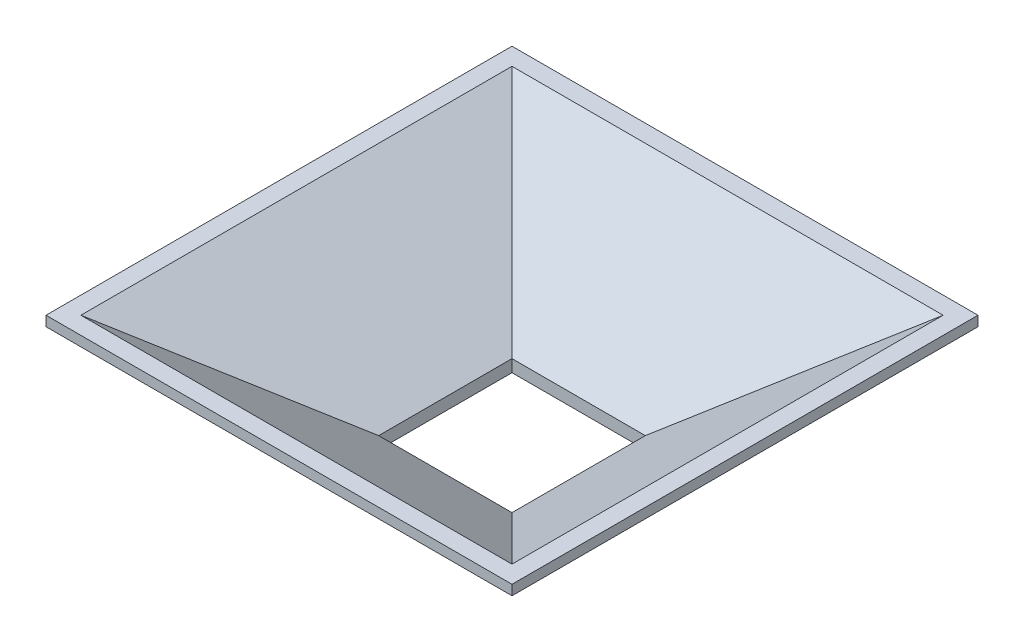
SolidWorks part; units mm, degrees
ref_plane "Front Plane" through (0, 0, 0) normal (0, 0, 1) x (1, 0, 0)
ref_plane "Top Plane" through (0, 0, 0) normal (0, 1, 0) x (1, 0, 0)
ref_plane "Right Plane" through (0, 0, 0) normal (1, 0, 0) x (0, 0, -1)
sketch "Sketch4" plane through (0, 0, 0) normal (0, 1, 0) x (1, 0, 0)
  line L1 (0, 0) -> (139.8, 0)
  line L2 (0, 0) -> (0, 139.8)
  line L3 (0, 139.8) -> (139.8, 139.8)
  line L4 (139.8, 0) -> (139.8, 139.8)
  dimension "D1" = 139.8
  dimension "D2" = 139.8
extrude "Boss-Extrude1" add sketch "Sketch4" against normal blind 60 draft 55
extrude "Boss-Extrude7" add sketch "Sketch4" against normal blind 3
shell "Shell5" thickness 3 removed face at (69.9, 0, -69.9)
sketch "Sketch9" plane through (0, 0, 0) normal (0, 1, 0) x (1, 0, 0)
  line L0 (49.9, 89.9) -> (89.9, 89.9)
  line L1 (69.9, 69.9) -> (5.2303, 134.5697) construction
  line L2 (69.9, 69.9) -> (134.5697, 134.5697) construction
  line L3 (89.9, 89.9) -> (89.9, 49.9)
  line L4 (69.9, 69.9) -> (134.5697, 5.2303) construction
  line L5 (89.9, 49.9) -> (49.9, 49.9)
  line L6 (69.9, 69.9) -> (5.2303, 5.2303) construction
  line L7 (49.9, 49.9) -> (49.9, 89.9)
  dimension "D1" = 40
extrude "Cut-Extrude3" cut sketch "Sketch9" against normal blind 65
